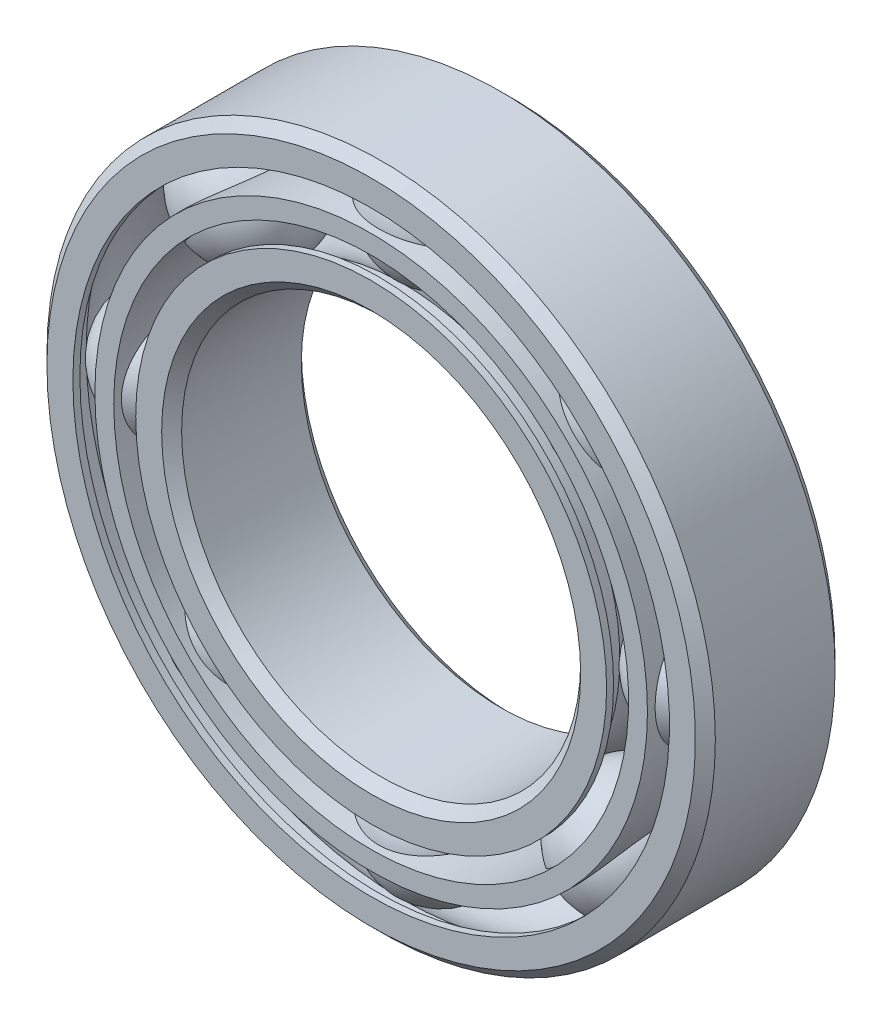
SolidWorks part; units mm, degrees
ref_plane "Front Plane" through (0, 0, 0) normal (0, 0, 1) x (1, 0, 0)
ref_plane "Top Plane" through (0, 0, 0) normal (0, 1, 0) x (1, 0, 0)
ref_plane "Right Plane" through (0, 0, 0) normal (1, 0, 0) x (0, 0, -1)
other "Configuration Table"
sketch "Sketch6" plane through (0, 0, 0) normal (0, 1, 0) x (1, 0, 0)
  line L0 (20, 0) -> (20, -14)
  line L1 (20, -14) -> (23.6, -14)
  line L2 (23.6, -14) -> (23.6, -13.3)
  line L3 (23.6, -13.3) -> (21.71, -13.3)
  line L4 (21.71, -13.3) -> (21.71, -10.78)
  line L5 (21.71, -0.7) -> (23.6, -0.7)
  line L6 (23.6, -0.7) -> (23.6, 0)
  line L7 (23.6, 0) -> (20, 0)
  line L12 (29.9, 0) -> (29.9, -0.7)
  line L13 (29.9, -0.7) -> (31.79, -0.7)
  line L14 (31.79, -0.7) -> (31.79, -3.22)
  line L15 (31.79, -13.3) -> (29.9, -13.3)
  line L16 (29.9, -13.3) -> (29.9, -14)
  line L17 (29.9, -14) -> (33.5, -14)
  line L18 (33.5, -14) -> (33.5, 0)
  line L19 (33.5, 0) -> (29.9, 0)
  line L20 (0, 14.5474) -> (0, -9.5086) construction
  line L21 (25.805, -7) -> (20, -7) construction
  line L22 (27.695, -14) -> (25.805, -14)
  line L23 (27.695, -14) -> (27.695, 0)
  line L24 (27.695, 0) -> (25.805, 0)
  line L25 (25.805, -14) -> (25.805, 0)
  line L26 (27.695, -14) -> (25.805, 0) construction
  line L27 (27.695, 0) -> (25.805, -14) construction
  line L28 (27.695, -7) -> (33.5, -7) construction
  line L29 (21.71, -3.22) -> (21.71, -0.7)
  line L30 (31.79, -10.78) -> (31.79, -13.3)
  arc A0 (21.71, -3.22) -> (21.71, -10.78) centre (26.75, -7) ccw
  arc A3 (31.79, -10.78) -> (31.79, -3.22) centre (26.75, -7) ccw
  point P32 (0, 0)
  point P35 (0, -9.5086)
  point P36 (0, 14.5474)
  dimension "D8" = 12.6
  dimension "D2" = 20
  dimension "D3" = 14
  dimension "D4" = 33.5
  dimension "D1" = 12.6
  dimension "D5" = 10.08
  dimension "D6" = 6.3
  dimension "D7" = 1.89
revolve "Revolve1" add sketch "Sketch6" angle 360 about L20
sketch "Sketch7" plane through (0, 0, 0) normal (0, 1, 0) x (1, 0, 0)
  line L0 (26.75, -0.7) -> (26.75, -13.3)
  line L1 (26.75, 1.2848) -> (26.75, -14.689) construction
  arc A0 (26.75, -13.3) -> (26.75, -0.7) centre (26.75, -7) ccw
  dimension "D1" = 12.6
revolve "Cut-Revolve1" cut sketch "Sketch7" angle 360 about L1 region at (29.4238, 0, 7)
pattern_circular "CirPattern1" count 8 over 360 about axis through (0, 0, 0) along (0, 0, -1) of "Cut-Revolve1"
revolve "Revolve2" add sketch "Sketch7<3>" angle 360 about L1
sketch "Sketch7<3>" plane through (0, 0, 0) normal (0, 1, 0) x (1, 0, 0) same geometry as "Sketch7"
pattern_circular "CirPattern2" count 8 over 360 about axis through (0, 0, 0) along (0, 0, -1) of "Revolve2"
chamfer "Chamfer2" distance 1 angle 45 2 edges at (-33.5, 0, 14) (-33.5, 0, 0)
ref_axis "bearing_axis" through (0, 0, 0) along (0, 0, 1)
ref_plane "down_face" through (0, 0, 0) normal (0, 0, -1) x (-1, 0, 0)
ref_plane "top_face" through (0, 0, 14) normal (0, 0, 1) x (1, 0, 0)
chamfer "Chamfer3" distance 1 angle 45 2 edges at (-20, 0, 0) (-20, 0, 14)
equation "\"inner_radius\" = 0.02m"
equation "\"outer_radius\" = 0.0335m"
equation "\"bearing_width\" = 0.014m"
equation "\"ball_radius\"= \"bearing_width\" / 2 * 0.9"
equation "\"ball_count\"= 8"
equation "\"chamfer_size\" = \"inner_radius\" / 20"
equation "\"D2@Sketch6\"=\"inner_radius\""
equation "\"D3@Sketch6\"=\"bearing_width\""
equation "\"D4@Sketch6\"=\"outer_radius\""
equation "\"D1@Sketch6\"=\"ball_radius\"*2"
equation "\"D5@Sketch6\"=\"ball_radius\"*1.6"
equation "\"D6@Sketch6\"=\"ball_radius\""
equation "\"D7@Sketch6\"=\"ball_radius\"*0.3"
equation "\"D8@Sketch6\"=\"ball_radius\"*2"
equation "\"D1@Sketch7\"=\"ball_radius\"*2"
equation "\"D1@CirPattern1\"=\"ball_count\""
equation "\"D1@CirPattern2\"=\"ball_count\""
equation "\"D1@Chamfer2\"= \"chamfer_size\""
equation "\"D1@Chamfer3\"=\"chamfer_size\""
